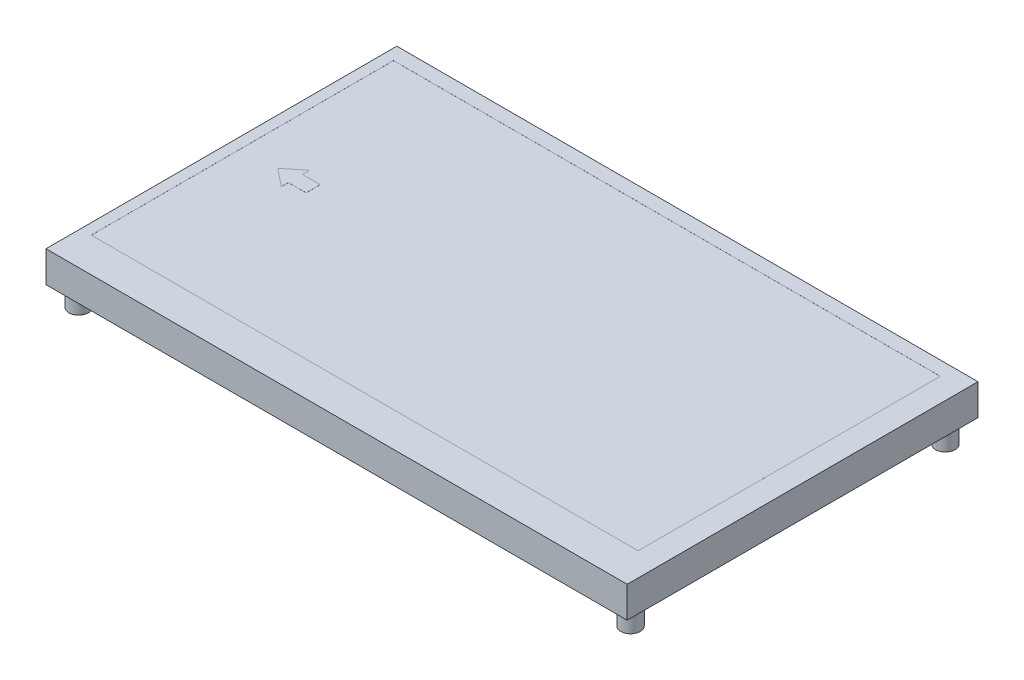
SolidWorks part; units mm, degrees
ref_plane "Front Plane" through (0, 0, 0) normal (0, 0, 1) x (1, 0, 0)
ref_plane "Top Plane" through (0, 0, 0) normal (0, 1, 0) x (1, 0, 0)
ref_plane "Right Plane" through (0, 0, 0) normal (1, 0, 0) x (0, 0, -1)
sketch "Sketch1" plane through (0, 0, 0) normal (0, 1, 0) x (1, 0, 0)
  line L1 (-82.14, 49.585) -> (82.14, 49.585)
  line L2 (-82.14, 49.585) -> (-82.14, -49.585)
  line L3 (-82.14, -49.585) -> (82.14, -49.585)
  line L4 (82.14, 49.585) -> (82.14, -49.585)
  line L5 (-82.14, 49.585) -> (82.14, -49.585) construction
  line L6 (-82.14, -49.585) -> (82.14, 49.585) construction
  point P0 (0, 0)
  dimension "D1" = 164.28
  dimension "D2" = 99.17
extrude "Boss-Extrude1" add sketch "Sketch1" along normal blind 8.8
sketch "Sketch2" plane through (0, 0, 0) normal (0, -1, 0) x (1, 0, 0)
  line L0 (0, 21.7771) -> (0, -10.6466) construction
  line L1 (-18.7928, 0) -> (14.2761, 0) construction
  circle A0 centre (-78, 44.5) radius 2.75
  circle A1 centre (78, 44.5) radius 2.75
  circle A2 centre (78, -44.5) radius 2.75
  circle A3 centre (-78, -44.5) radius 2.75
  circle A4 centre (-78, 44.5) radius 1.25
  circle A5 centre (78, 44.5) radius 1.25
  circle A6 centre (78, -44.5) radius 1.25
  circle A7 centre (-78, -44.5) radius 1.25
  dimension "D3" = 5.5
  dimension "D4" = 2.5
  dimension "D1" = 156
  dimension "D2" = 89
extrude "Boss-Extrude2" add sketch "Sketch2" along normal blind 6
sketch "Sketch3" plane through (0, 8.8, 0) normal (0, 1, 0) x (1, 0, 0)
  line L0 (82.14, -49.585) -> (82.14, 49.585) construction
  line L1 (-82.14, -49.585) -> (82.14, -49.585) construction
  line L2 (82.14, 49.585) -> (-82.14, 49.585) construction
  line L3 (-79.08, -39.855) -> (75.49, -39.855)
  line L4 (-79.08, -39.855) -> (-79.08, 45.585)
  line L5 (-79.08, 45.585) -> (75.49, 45.585)
  line L6 (75.49, -39.855) -> (75.49, 45.585)
  line L7 (-79.08, -39.855) -> (75.49, 45.585) construction
  line L8 (-79.08, 45.585) -> (75.49, -39.855) construction
  line L9 (-82.14, 49.585) -> (-82.14, -49.585) construction
  line L10 (-1.795, 45.585) -> (-1.795, -39.855) construction
  line L16 (-79.08, -39.855) -> (-79.08, 45.585)
  line L17 (75.49, -39.855) -> (75.49, 45.585)
  line L20 (-79.08, 2.865) -> (75.49, 2.865) construction
  line L21 (65.49, 2.865) -> (60.49, 6.865) construction
  line L22 (60.49, 6.865) -> (60.49, 4.865) construction
  line L23 (60.49, 4.865) -> (55.49, 4.865) construction
  line L24 (60.49, 0.865) -> (55.49, 0.865) construction
  line L25 (60.49, -1.135) -> (60.49, 0.865) construction
  line L26 (65.49, 2.865) -> (60.49, -1.135) construction
  line L27 (55.49, 4.865) -> (55.49, 0.865) construction
  line L28 (-64.08, -1.135) -> (-64.08, 0.865)
  line L29 (-69.08, 2.865) -> (-64.08, -1.135)
  line L30 (-69.08, 2.865) -> (-64.08, 6.865)
  line L31 (-64.08, 6.865) -> (-64.08, 4.865)
  line L32 (-64.08, 4.865) -> (-59.08, 4.865)
  line L33 (-59.08, 4.865) -> (-59.08, 0.865)
  line L34 (-64.08, 0.865) -> (-59.08, 0.865)
  point P4 (-1.795, 2.865)
  point P14 (0, 0)
  dimension "D1" = 4
  dimension "D2" = 3.06
  dimension "D3" = 6.65
  dimension "D4" = 9.73
  dimension "D10" = 5
  dimension "D11" = 4
  dimension "D12" = 5
  dimension "D13" = 8
  dimension "D14" = 10
extrude "Cut-Extrude1" cut sketch "Sketch3" against normal blind 0.01 contours L3 L6 L5 L4 region at (-1.607, 8.8, -2.865)
sketch "Sketch4" plane through (-82.14, 0, 0) normal (-1, 0, 0) x (0, 0, 1)
  line L0 (31.685, -1.51) -> (37.585, -1.51) construction
  line L1 (31.685, -0.01) -> (37.585, -0.01)
  line L2 (31.685, -3.01) -> (37.585, -3.01)
  line L3 (49.585, 8.8) -> (49.585, 0) construction
  line L5 (31.685, -0.16) -> (37.585, -0.16)
  line L6 (31.685, -2.86) -> (37.585, -2.86)
  line L7 (-49.585, 0) -> (49.585, 0) construction
  arc A0 (31.685, -0.01) -> (31.685, -3.01) centre (31.685, -1.51) ccw
  arc A1 (37.585, -3.01) -> (37.585, -0.01) centre (37.585, -1.51) ccw
  arc A2 (37.585, -2.86) -> (37.585, -0.16) centre (37.585, -1.51) ccw
  arc A3 (31.685, -0.16) -> (31.685, -2.86) centre (31.685, -1.51) ccw
  point P2 (34.635, -1.51)
  point P7 (30.185, -1.51)
  point P8 (39.085, -1.51)
  dimension "D1" = 8.9
  dimension "D2" = 3
  dimension "D3" = 10.5
  dimension "D5" = 0.01
  dimension "D4" = 0.15
extrude "Boss-Extrude3" add sketch "Sketch4" against normal blind 7.3
sketch "Sketch5" plane through (0, 0, 0) normal (0, -1, 0) x (1, 0, 0)
  line L0 (-80.75, 44.5) -> (-75.25, 44.5) construction
  line L1 (-69.9, 47.5) -> (-66.1, 47.5)
  line L2 (-69.9, 47.5) -> (-69.9, 44.5)
  line L3 (-69.9, 44.5) -> (-66.1, 44.5)
  line L4 (-66.1, 47.5) -> (-66.1, 44.5)
  line L5 (-69.9, 47.5) -> (-66.1, 44.5) construction
  line L6 (-69.9, 44.5) -> (-66.1, 47.5) construction
  line L11 (0, 49.585) -> (0, -49.585) construction
  line L12 (-82.14, 49.585) -> (82.14, 49.585) construction
  line L13 (82.14, -49.585) -> (-82.14, -49.585) construction
  line L14 (69.9, 47.5) -> (66.1, 47.5)
  line L15 (69.9, 47.5) -> (69.9, 44.5)
  line L16 (69.9, 44.5) -> (66.1, 44.5)
  line L17 (66.1, 47.5) -> (66.1, 44.5)
  circle A0 centre (-78, 44.5) radius 2.75 construction
  circle A1 centre (-78, 44.5) radius 2.75 construction
  point P0 (-68, 46)
  dimension "D1" = 3.8
  dimension "D2" = 3
  dimension "D3" = 10
extrude "Boss-Extrude4" add sketch "Sketch5" along normal blind 1.2
